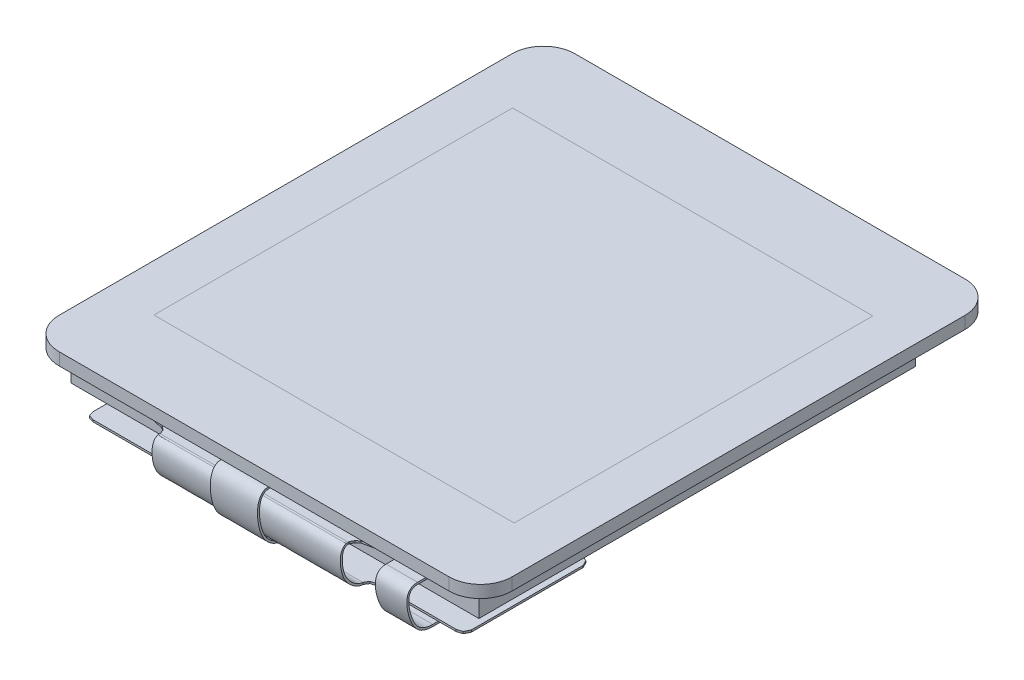
SolidWorks part; units mm, degrees
ref_plane "Ebene vorne" through (0, 0, 0) normal (0, 0, 1) x (1, 0, 0)
ref_plane "Ebene oben" through (0, 0, 0) normal (0, 1, 0) x (1, 0, 0)
ref_plane "Ebene rechts" through (0, 0, 0) normal (1, 0, 0) x (0, 0, -1)
sketch "Skizze1" plane through (0, 0, 0) normal (0, 1, 0) x (1, 0, 0)
  line L0 (-10.3006, -18.7379) -> (-10.4888, -18.361)
  line L1 (10.2585, -18.6958) -> (10.4, -18.361)
  line L4 (-14.0273, -22.8411) -> (-14.0273, -22.7993)
  line L5 (-14.0273, -22.7993) -> (-14.0691, -22.7993)
  line L6 (-14.0691, -22.7993) -> (-14.0691, -22.8411)
  line L7 (-14.0691, -22.8411) -> (-14.0273, -22.8411)
  line L8 (15.7018, -18.361) -> (15.7018, 15.346)
  line L9 (15.7018, 15.346) -> (-15.7858, 15.346)
  line L10 (-15.7858, 15.346) -> (-15.7858, -18.361)
  line L11 (-15.7858, -18.361) -> (15.7018, -18.361)
  line L12 (12.5614, -22.7993) -> (12.5614, -18.361)
  line L13 (10.1331, -22.7993) -> (10.1331, -18.361)
  line L14 (10.1331, -26.3167) -> (10.1331, -18.361)
  line L15 (12.5614, -26.3167) -> (12.5614, -18.361)
  line L16 (10.7611, -26.3167) -> (10.1331, -26.3167)
  line L17 (11.724, -26.3167) -> (10.9705, -26.3167)
  line L18 (11.5986, -26.0233) -> (11.5146, -26.3167)
  line L19 (11.1799, -26.3167) -> (11.0959, -26.0234)
  line L20 (10.9705, -26.3167) -> (10.9705, -26.2327)
  line L21 (10.9705, -26.2327) -> (10.8448, -26.1909)
  line L22 (10.8448, -26.1909) -> (10.7612, -26.2327)
  line L23 (10.7612, -26.2327) -> (10.7612, -26.3167)
  line L24 (10.6354, -26.0233) -> (10.4678, -26.3167)
  line L25 (12.2267, -26.3167) -> (12.1009, -26.0234)
  line L26 (12.0173, -26.3167) -> (11.9334, -26.2327)
  line L27 (11.9334, -26.2327) -> (11.8916, -26.1909)
  line L28 (11.8916, -26.1909) -> (11.724, -26.2327)
  line L29 (11.724, -26.2327) -> (11.724, -26.3167)
  line L30 (12.5614, -26.3167) -> (12.0173, -26.3167)
  line L31 (11.5986, -25.0187) -> (11.5986, -24.0137)
  line L32 (11.5986, -24.0137) -> (12.1009, -24.0137)
  line L33 (12.1009, -24.0137) -> (12.1009, -25.0187)
  line L34 (11.5986, -25.0187) -> (11.5146, -25.2699)
  line L35 (11.5146, -25.2699) -> (11.5986, -25.4792)
  line L36 (11.8915, -25.1441) -> (11.724, -25.1859)
  line L37 (11.724, -25.1859) -> (11.724, -25.3535)
  line L38 (11.724, -25.3535) -> (11.8915, -25.3953)
  line L39 (11.8915, -25.3953) -> (11.9334, -25.3535)
  line L40 (11.9334, -25.3535) -> (12.0173, -25.2699)
  line L41 (12.0173, -25.2699) -> (11.9334, -25.1859)
  line L42 (11.9334, -25.1859) -> (11.8915, -25.1441)
  line L43 (12.1009, -25.4792) -> (12.2267, -25.2699)
  line L44 (12.2267, -25.2699) -> (12.1009, -25.0187)
  line L45 (10.6354, -25.3535) -> (10.6354, -24.0137)
  line L46 (11.0959, -24.0137) -> (11.0959, -25.3535)
  line L47 (11.0959, -25.814) -> (11.0959, -26.0234)
  line L48 (10.6354, -25.814) -> (10.6354, -26.0234)
  line L49 (10.6354, -25.3535) -> (10.4678, -25.5628)
  line L50 (10.4678, -25.5628) -> (10.6354, -25.814)
  line L51 (10.8447, -25.3953) -> (10.7612, -25.4792)
  line L52 (10.7612, -25.4792) -> (10.7612, -25.6046)
  line L53 (10.7612, -25.6046) -> (10.8447, -25.6886)
  line L54 (10.8447, -25.6886) -> (10.9705, -25.6046)
  line L55 (10.9705, -25.6046) -> (10.9705, -25.4792)
  line L56 (10.9705, -25.4792) -> (10.8447, -25.3953)
  line L57 (11.0959, -25.814) -> (11.1799, -25.5628)
  line L58 (11.1799, -25.5628) -> (11.0959, -25.3535)
  line L59 (12.1009, -26.0233) -> (12.1009, -25.4792)
  line L60 (11.5986, -25.4792) -> (11.5986, -26.0233)
  line L61 (10.6354, -24.0137) -> (11.0959, -24.0137)
  line L62 (-13.9015, -13.8387) -> (-13.9015, 13.8387)
  line L63 (-13.9015, 13.8387) -> (13.9015, 13.8387)
  line L64 (13.9015, 13.8387) -> (13.9015, -13.8387)
  line L65 (13.9015, -13.8387) -> (-13.9015, -13.8387)
  line L77 (-7.3278, -19.8683) -> (-7.3278, -22.3806)
  line L78 (-10.1749, -18.8215) -> (-7.7465, -19.366)
  line L80 (-10.3006, -18.7379) -> (-10.1749, -18.8215)
  line L81 (-7.3278, -19.8683) -> (-7.4532, -19.5754)
  line L82 (-7.4532, -19.5754) -> (-7.7465, -19.366)
  line L83 (-7.3278, -19.8683) -> (-7.3278, -22.3806)
  line L84 (-7.7883, -22.8411) -> (-7.4532, -22.7158)
  line L85 (-7.4532, -22.7158) -> (-7.3278, -22.3806)
  line L86 (10.0491, -18.8215) -> (7.6207, -19.366)
  line L87 (10.0491, -18.8215) -> (10.2167, -18.7379)
  line L88 (10.2167, -18.7379) -> (10.2585, -18.6958)
  line L89 (7.6207, -19.366) -> (7.3696, -19.5754)
  line L90 (7.3696, -19.5754) -> (7.202, -19.8683)
  line L91 (7.202, -19.8683) -> (7.202, -22.3806)
  line L92 (3.5171, -58.2648) -> (-3.5593, -58.2648)
  line L93 (3.7265, -52.8214) -> (-3.7686, -52.8214)
  line L94 (3.5171, -58.2648) -> (3.6847, -58.223)
  line L95 (3.6847, -58.223) -> (3.7265, -58.0554)
  line L96 (3.7265, -53.2823) -> (3.7265, -33.8118)
  line L97 (-3.7687, -58.0554) -> (-3.6994, -58.223)
  line L98 (-3.6994, -58.223) -> (-3.5593, -58.2648)
  line L99 (-3.7687, -52.8214) -> (3.7265, -52.8214)
  line L100 (3.7265, -53.2823) -> (3.7265, -58.0554)
  line L101 (3.5171, -58.2648) -> (3.6847, -58.223)
  line L102 (3.6847, -58.223) -> (3.7265, -58.0554)
  line L103 (3.5171, -58.2648) -> (-3.5593, -58.2648)
  line L104 (-3.7687, -58.0554) -> (-3.6994, -58.223)
  line L105 (-3.6994, -58.223) -> (-3.5593, -58.2648)
  line L107 (-3.7687, -58.0554) -> (-3.7687, -33.8118)
  line L108 (-3.7687, -33.8118) -> (-4.1034, -32.9744)
  line L109 (-4.1034, -32.9744) -> (-5.0248, -32.6393)
  line L114 (13.9433, -22.8411) -> (7.7883, -22.8411)
  line L115 (-7.7883, -22.8411) -> (-14.0691, -22.8411)
  line L116 (-14.0691, -22.8411) -> (-14.4878, -22.9669)
  line L117 (-14.4878, -22.9669) -> (-14.6132, -23.3856)
  line L118 (7.202, -22.3806) -> (7.4114, -22.7158)
  line L119 (7.4114, -22.7158) -> (7.7883, -22.8412)
  line L120 (14.5714, -23.3856) -> (14.5714, -32.0112)
  line L121 (14.5714, -23.3856) -> (14.3621, -22.9669)
  line L122 (14.3621, -22.9669) -> (13.9434, -22.8412)
  line L123 (13.9433, -32.6393) -> (4.9409, -32.6393)
  line L124 (4.9409, -32.6393) -> (4.1034, -32.9744)
  line L125 (4.1034, -32.9744) -> (3.7265, -33.8118)
  line L126 (13.9433, -32.6393) -> (14.3621, -32.4299)
  line L127 (14.3621, -32.4299) -> (14.5714, -32.0112)
  line L128 (-5.0248, -32.6393) -> (-14.0691, -32.6393)
  line L129 (-14.6132, -23.3856) -> (-14.6132, -32.0112)
  line L130 (-14.6132, -32.0112) -> (-14.4878, -32.4299)
  line L131 (-14.4878, -32.4299) -> (-14.0691, -32.6393)
  line L132 (-3.0566, -25.3535) -> (-2.7219, -25.1859)
  line L133 (-2.7219, -25.1859) -> (-2.5961, -24.8512)
  line L134 (-2.5961, -24.8511) -> (-2.5961, -19.9519)
  line L135 (1.0466, -24.8511) -> (1.256, -25.1859)
  line L136 (1.256, -25.1859) -> (1.5911, -25.3535)
  line L137 (1.0466, -24.8511) -> (1.0466, -19.9519)
  line L138 (-8.5, -31.2995) -> (-11.3474, -31.2995)
  line L139 (-11.4728, -31.0901) -> (-11.4728, -31.2574)
  line L140 (-11.4728, -31.2574) -> (-11.3474, -31.2995)
  line L141 (-11.4728, -31.0901) -> (-11.4728, -27.9916)
  line L142 (-11.3474, -27.7822) -> (-11.4728, -27.824)
  line L143 (-11.4728, -27.824) -> (-11.4728, -27.9916)
  line L144 (-11.3474, -27.7822) -> (-8.5, -27.7822)
  line L145 (-8.5, -27.7822) -> (-8.5, -31.2995)
  line L146 (-11.4728, -31.0901) -> (-11.4728, -31.2574)
  line L147 (-11.4728, -31.2574) -> (-11.3474, -31.2995)
  line L148 (-11.4728, -31.0901) -> (-11.4728, -27.9916)
  line L149 (-11.3474, -27.7822) -> (-11.4728, -27.824)
  line L150 (-11.4728, -27.824) -> (-11.4728, -27.9916)
  line L151 (-11.3474, -27.7822) -> (-5.0248, -27.7822)
  line L152 (-5.0248, -27.7822) -> (-4.6897, -27.6146)
  line L153 (-4.6897, -27.6146) -> (-4.5221, -27.2795)
  line L154 (-14.0273, -22.8411) -> (-14.0273, -22.7993)
  line L155 (-14.0273, -22.7993) -> (-14.0691, -22.7993)
  line L156 (-14.0691, -22.7993) -> (-14.0691, -22.8411)
  line L157 (-14.0691, -22.8411) -> (-14.0273, -22.8411)
  line L158 (10.6354, -27.3635) -> (10.6354, -23.8044)
  line L159 (10.6354, -23.8044) -> (11.0959, -23.8044)
  line L160 (11.0959, -23.8044) -> (11.0959, -27.3635)
  line L161 (11.0959, -27.3635) -> (10.6354, -27.3635)
  line L162 (11.5986, -27.3635) -> (11.5986, -23.8044)
  line L163 (11.5986, -23.8044) -> (12.1009, -23.8044)
  line L164 (12.1009, -23.8044) -> (12.1009, -27.3635)
  line L165 (12.1009, -27.3635) -> (11.5986, -27.3635)
  line L166 (10.7611, -28.8708) -> (10.7611, -28.0334)
  line L167 (11.1799, -28.4521) -> (10.3424, -28.4521)
  line L168 (11.6822, -28.4521) -> (12.4778, -28.4521)
  line L169 (-7.7883, -24.1813) -> (-7.7883, -23.8044)
  line L170 (-7.7883, -23.8044) -> (-5.9877, -23.8044)
  line L171 (-5.9877, -23.8044) -> (-5.9877, -24.1813)
  line L172 (-5.9877, -24.1813) -> (-7.7883, -24.1813)
  line L173 (-7.7883, -24.8511) -> (-7.7883, -24.516)
  line L174 (-7.7883, -24.516) -> (-5.9877, -24.516)
  line L175 (-5.9877, -24.516) -> (-5.9877, -24.8511)
  line L176 (-5.9877, -24.8511) -> (-7.7883, -24.8511)
  line L177 (-7.7883, -25.4792) -> (-7.7883, -25.1441)
  line L178 (-7.7883, -25.1441) -> (-5.9877, -25.1441)
  line L179 (-5.9877, -25.1441) -> (-5.9877, -25.4792)
  line L180 (-5.9877, -25.4792) -> (-7.7883, -25.4792)
  line L181 (-7.7883, -26.1073) -> (-7.7883, -25.7722)
  line L182 (-7.7883, -25.7722) -> (-5.9877, -25.7722)
  line L183 (-5.9877, -25.7722) -> (-5.9877, -26.1073)
  line L184 (-5.9877, -26.1073) -> (-7.7883, -26.1073)
  line L185 (-11.8079, -24.1813) -> (-11.8079, -23.8044)
  line L186 (-11.8079, -23.8044) -> (-13.6504, -23.8044)
  line L187 (-13.6504, -23.8044) -> (-13.6504, -24.1813)
  line L188 (-13.6504, -24.1813) -> (-11.8079, -24.1813)
  line L189 (-11.8079, -24.8511) -> (-11.8079, -24.516)
  line L190 (-11.8079, -24.516) -> (-13.6504, -24.516)
  line L191 (-13.6504, -24.516) -> (-13.6504, -24.8511)
  line L192 (-13.6504, -24.8511) -> (-11.8079, -24.8511)
  line L193 (-11.8079, -25.4792) -> (-11.8079, -25.1441)
  line L194 (-11.8079, -25.1441) -> (-13.6504, -25.1441)
  line L195 (-13.6504, -25.1441) -> (-13.6504, -25.4792)
  line L196 (-13.6504, -25.4792) -> (-11.8079, -25.4792)
  line L197 (-11.8079, -26.1073) -> (-11.8079, -25.7722)
  line L198 (-11.8079, -25.7722) -> (-13.6504, -25.7722)
  line L199 (-13.6504, -25.7722) -> (-13.6504, -26.1073)
  line L200 (-13.6504, -26.1073) -> (-11.8079, -26.1073)
  line L201 (-11.3474, -31.2995) -> (-5.0248, -31.2995)
  line L202 (-4.5221, -31.8018) -> (-4.6897, -31.4667)
  line L203 (-4.6897, -31.4667) -> (-5.0248, -31.2995)
  line L204 (1.8005, -31.8018) -> (1.9262, -31.8018)
  line L205 (1.9262, -31.8018) -> (2.0098, -31.6343)
  line L206 (2.0098, -31.6343) -> (2.0098, -25.5628)
  line L207 (2.0098, -25.5628) -> (1.9262, -25.3953)
  line L208 (1.9262, -25.3953) -> (1.8005, -25.3535)
  line L209 (1.8005, -25.3535) -> (-4.3128, -25.3535)
  line L210 (-4.3128, -25.3535) -> (-4.4803, -25.3953)
  line L211 (-4.4803, -25.3953) -> (-4.5221, -25.5628)
  line L212 (-4.5221, -25.5628) -> (-4.5221, -31.6343)
  line L213 (-4.5221, -31.6343) -> (-4.4803, -31.8018)
  line L214 (-4.4803, -31.8018) -> (-4.3128, -31.8018)
  line L215 (-4.3128, -31.8018) -> (1.8005, -31.8018)
  line L216 (14.9901, -19.9519) -> (16.2463, -19.6589)
  line L217 (16.2463, -19.6589) -> (17.1674, -18.7379)
  line L218 (17.1674, -18.7379) -> (17.4189, -17.5235)
  line L219 (17.4189, -17.5235) -> (17.4189, 17.4396)
  line L220 (17.4189, 17.4396) -> (17.1674, 18.6957)
  line L221 (17.1674, 18.6957) -> (16.2463, 19.575)
  line L222 (16.2463, 19.575) -> (14.9902, 19.8683)
  line L223 (14.9901, 19.8683) -> (-15.0741, 19.8683)
  line L224 (-15.0741, 19.8683) -> (-16.2881, 19.575)
  line L225 (-16.2881, 19.575) -> (-17.1677, 18.6957)
  line L226 (-17.1677, 18.6957) -> (-17.5442, 17.4396)
  line L227 (-17.5443, 17.4396) -> (-17.5443, -17.5236)
  line L228 (-17.5443, -17.5235) -> (-17.1677, -18.7379)
  line L229 (-17.1677, -18.7379) -> (-16.2881, -19.6589)
  line L230 (-16.2881, -19.6589) -> (-15.0741, -19.9519)
  line L231 (-15.0741, -19.9519) -> (14.9902, -19.9519)
  line L232 (-13.9015, 13.8387) -> (-13.9015, -13.8387)
  line L233 (-13.9015, -13.8387) -> (13.9015, -13.8387)
  line L234 (13.9015, -13.8387) -> (13.9015, 13.8387)
  line L235 (13.9015, 13.8387) -> (-13.9015, 13.8387)
  line L236 (-12.5659, -28.1971) -> (-12.5659, -28.5322)
  line L237 (-12.5659, -28.5322) -> (-13.3197, -28.5322)
  line L238 (-13.3197, -28.5322) -> (-13.3197, -28.1971)
  line L239 (-13.3197, -28.1971) -> (-12.5659, -28.1971)
  line L240 (-12.5659, -28.6998) -> (-12.5659, -29.0349)
  line L241 (-12.5659, -29.0349) -> (-13.3197, -29.0349)
  line L242 (-13.3197, -29.0349) -> (-13.3197, -28.6998)
  line L243 (-13.3197, -28.6998) -> (-12.5659, -28.6998)
  line L244 (-12.5659, -29.2439) -> (-12.5659, -29.4951)
  line L245 (-12.5659, -29.4951) -> (-13.3197, -29.4951)
  line L246 (-13.3197, -29.4951) -> (-13.3197, -29.2439)
  line L247 (-13.3197, -29.2439) -> (-12.5659, -29.2439)
  line L248 (-12.5659, -29.7048) -> (-12.5659, -29.9977)
  line L249 (-12.5659, -29.9977) -> (-13.3197, -29.9977)
  line L250 (-13.3197, -29.9977) -> (-13.3197, -29.7048)
  line L251 (-13.3197, -29.7048) -> (-12.5659, -29.7048)
  line L252 (-12.5659, -30.2071) -> (-12.5659, -30.5001)
  line L253 (-12.5659, -30.5001) -> (-13.3197, -30.5001)
  line L254 (-13.3197, -30.5001) -> (-13.3197, -30.2071)
  line L255 (-13.3197, -30.2071) -> (-12.5659, -30.2071)
  line L256 (-12.5659, -30.7094) -> (-12.5659, -31.0446)
  line L257 (-12.5659, -31.0446) -> (-13.3197, -31.0446)
  line L258 (-13.3197, -31.0446) -> (-13.3197, -30.7094)
  line L259 (-13.3197, -30.7094) -> (-12.5659, -30.7094)
  point P1 (0, 0)
  point P2 (0, 0)
  point P82 (0, 0)
  point P84 (0, 0)
sketch "Skizze3" plane through (0, 0, 0) normal (0, 1, 0) x (1, 0, 0)
  line L0 (15.7018, -18.361) -> (15.7018, 15.346)
  line L1 (-15.7858, 15.346) -> (15.7018, 15.346)
  line L2 (-15.7858, 15.346) -> (-15.7858, -18.361)
  line L3 (-15.7858, -18.361) -> (15.7018, -18.361)
  point P0 (0, 0)
extrude "Aufsatz-Linear austragen1" add sketch "Skizze3" along normal blind 2.275
sketch "Skizze2" plane through (0, 0, 0) normal (0, 1, 0) x (1, 0, 0)
  line L3 (17.4189, -17.5232) -> (17.4189, 17.4396)
  line L7 (14.9901, 19.8683) -> (-15.0741, 19.8683)
  line L11 (-17.5443, 17.4396) -> (-17.5443, -17.5236)
  line L15 (-15.0741, -19.9519) -> (14.9902, -19.9519)
  arc A0 (-17.5443, 17.4396) -> (-15.0741, 19.8683) centre (-15.1152, 17.4396) cw
  arc A1 (14.9901, 19.8683) -> (17.4189, 17.4396) centre (14.9901, 17.4396) cw
  arc A2 (-17.5443, -17.5236) -> (-15.0741, -19.9519) centre (-15.1156, -17.5236) ccw
  arc A3 (14.9902, -19.9519) -> (17.4189, -17.5232) centre (14.9902, -17.5232) ccw
  point P0 (0, 0)
extrude "Aufsatz-Linear austragen2" add sketch "Skizze2" along normal offset from surface (0.95 mm away) 3.225 from surface separate body up to face at (-0.042, 0, 1.5075) starting at face at (-0.042, 2.275, 1.5075)
sketch "Skizze4" plane through (0, 3.225, 0) normal (0, 1, 0) x (1, 0, 0)
  line L0 (-13.9015, -13.8387) -> (-13.9015, 13.8387)
  line L1 (-13.9015, 13.8387) -> (13.9015, 13.8387)
  line L2 (13.9015, 13.8387) -> (13.9015, -13.8387)
  line L3 (13.9015, -13.8387) -> (-13.9015, -13.8387)
  point P0 (0, 0)
split line "Trennlinie1"
sketch "Skizze5" plane through (0, 0, 0) normal (0, 1, 0) x (1, 0, 0)
  line L0 (-10.3006, -18.7379) -> (-10.4888, -18.361)
  line L1 (-7.3278, -19.9519) -> (7.202, -19.9519)
  line L7 (-7.3278, -19.8683) -> (-7.4532, -19.5754)
  line L9 (10.0491, -18.8215) -> (7.6207, -19.366)
  line L10 (7.202, -19.9519) -> (7.202, -19.8683)
  line L11 (-15.0741, -19.9519) -> (14.9902, -19.9519) construction
  line L12 (7.3696, -19.5754) -> (7.6207, -19.366)
  line L13 (7.3696, -19.5754) -> (7.202, -19.8683)
  line L14 (10.0491, -18.8215) -> (10.1331, -18.7796)
  line L15 (-10.3006, -18.7379) -> (-10.1749, -18.8215)
  line L16 (-7.7465, -19.366) -> (-7.4532, -19.5754)
  line L17 (-10.4888, -18.361) -> (12.5614, -18.361)
  line L18 (10.1331, -19.9519) -> (12.5614, -19.9519)
  line L19 (-7.3278, -19.8683) -> (-7.3278, -19.9519)
  line L20 (10.1331, -18.7796) -> (10.1331, -19.9519)
  line L21 (12.5614, -18.361) -> (12.5614, -19.9519)
  line L22 (-10.1749, -18.8215) -> (-7.7465, -19.366)
  point P1 (0, 0)
extrude "Aufsatz-Linear austragen3" add sketch "Skizze5" along normal blind 0.15 from offset 1.5 separate body contours L15 L22 L16 L7 L19 L1 L10 L13 L12 L9 L14 L20 L18 L21 L17 L0 region at (1.315, 0, 19.1017)
sketch "Skizze6" plane through (0, 0, 0) normal (0, 1, 0) x (1, 0, 0)
  line L2 (-2.5961, -19.9519) -> (-2.5961, -18.361)
  line L3 (-15.7858, -18.361) -> (15.7018, -18.361) construction
  line L4 (-2.5961, -19.9519) -> (1.0466, -19.9519)
  line L5 (-2.5961, -18.361) -> (1.0466, -18.361)
  line L6 (-10.4888, -18.361) -> (12.5614, -18.361) construction
  line L7 (1.0466, -18.361) -> (1.0466, -19.9519)
  point P0 (0, 0)
extrude "Aufsatz-Linear austragen4" add sketch "Skizze6" against normal blind 0.15 from surface separate body starting at face at (-0.042, 2.275, 1.5075)
sketch "Skizze7" plane through (0, 0, 0) normal (0, 1, 0) x (1, 0, 0)
  line L194 (-13.3197, -10.4927) -> (-12.5659, -10.4927)
  line L195 (-13.3197, -10.1576) -> (-13.3197, -10.4927)
  line L196 (-12.5659, -10.1576) -> (-13.3197, -10.1576)
  line L197 (-12.5659, -10.4927) -> (-12.5659, -10.1576)
  line L198 (-13.3197, -10.995) -> (-12.5659, -10.995)
  line L199 (-13.3197, -10.7021) -> (-13.3197, -10.995)
  line L200 (-12.5659, -10.7021) -> (-13.3197, -10.7021)
  line L201 (-12.5659, -10.995) -> (-12.5659, -10.7021)
  line L202 (-13.3197, -11.4974) -> (-12.5659, -11.4974)
  line L203 (-13.3197, -11.2044) -> (-13.3197, -11.4974)
  line L204 (-12.5659, -11.2044) -> (-13.3197, -11.2044)
  line L205 (-12.5659, -11.4974) -> (-12.5659, -11.2044)
  line L206 (-13.3197, -11.9582) -> (-12.5659, -11.9582)
  line L207 (-13.3197, -11.7071) -> (-13.3197, -11.9582)
  line L208 (-12.5659, -11.7071) -> (-13.3197, -11.7071)
  line L209 (-12.5659, -11.9582) -> (-12.5659, -11.7071)
  line L210 (-13.3197, -12.5023) -> (-12.5659, -12.5023)
  line L211 (-13.3197, -12.1672) -> (-13.3197, -12.5023)
  line L212 (-12.5659, -12.1672) -> (-13.3197, -12.1672)
  line L213 (-12.5659, -12.5023) -> (-12.5659, -12.1672)
  line L214 (-13.3197, -13.005) -> (-12.5659, -13.005)
  line L215 (-13.3197, -12.6699) -> (-13.3197, -13.005)
  line L216 (-12.5659, -12.6699) -> (-13.3197, -12.6699)
  line L217 (-12.5659, -13.005) -> (-12.5659, -12.6699)
  line L218 (-9.5538, -5.8259) -> (-3.4405, -5.8259)
  line L219 (-9.7213, -5.8259) -> (-9.5537, -5.8259)
  line L220 (-9.7631, -5.9934) -> (-9.7213, -5.8259)
  line L221 (-9.7631, -12.0649) -> (-9.7631, -5.9934)
  line L222 (-9.7213, -12.2324) -> (-9.7631, -12.0649)
  line L223 (-9.5538, -12.2742) -> (-9.7213, -12.2324)
  line L224 (-3.4405, -12.2742) -> (-9.5537, -12.2742)
  line L225 (-3.3147, -12.2324) -> (-3.4405, -12.2742)
  line L226 (-3.2311, -12.0649) -> (-3.3147, -12.2324)
  line L227 (-3.2311, -5.9934) -> (-3.2311, -12.0649)
  line L228 (-3.3147, -5.8259) -> (-3.2311, -5.9934)
  line L229 (-3.4405, -5.8259) -> (-3.3147, -5.8259)
  line L230 (-9.9307, -6.161) -> (-10.2658, -6.3282)
  line L231 (-9.7631, -5.8259) -> (-9.9307, -6.161)
  line L232 (-11.3474, -9.9026) -> (-5.0248, -9.9026)
  line L233 (-13.6504, -15.0948) -> (-11.8079, -15.0948)
  line L234 (-13.6504, -15.43) -> (-13.6504, -15.0948)
  line L235 (-11.8079, -15.43) -> (-13.6504, -15.43)
  line L236 (-11.8079, -15.0948) -> (-11.8079, -15.43)
  line L237 (-13.6504, -15.7229) -> (-11.8079, -15.7229)
  line L238 (-13.6504, -16.058) -> (-13.6504, -15.7229)
  line L239 (-11.8079, -16.058) -> (-13.6504, -16.058)
  line L240 (-11.8079, -15.7229) -> (-11.8079, -16.058)
  line L241 (-13.6504, -16.351) -> (-11.8079, -16.351)
  line L242 (-13.6504, -16.6861) -> (-13.6504, -16.351)
  line L243 (-11.8079, -16.6861) -> (-13.6504, -16.6861)
  line L244 (-11.8079, -16.351) -> (-11.8079, -16.6861)
  line L245 (-13.6504, -17.0209) -> (-11.8079, -17.0209)
  line L246 (-13.6504, -17.3978) -> (-13.6504, -17.0209)
  line L247 (-11.8079, -17.3978) -> (-13.6504, -17.3978)
  line L248 (-11.8079, -17.0209) -> (-11.8079, -17.3978)
  line L249 (-5.9877, -15.0948) -> (-7.7883, -15.0948)
  line L250 (-5.9877, -15.43) -> (-5.9877, -15.0948)
  line L251 (-7.7883, -15.43) -> (-5.9877, -15.43)
  line L252 (-7.7883, -15.0948) -> (-7.7883, -15.43)
  line L253 (-5.9877, -15.7229) -> (-7.7883, -15.7229)
  line L254 (-5.9877, -16.058) -> (-5.9877, -15.7229)
  line L255 (-7.7883, -16.058) -> (-5.9877, -16.058)
  line L256 (-7.7883, -15.7229) -> (-7.7883, -16.058)
  line L257 (-5.9877, -16.351) -> (-7.7883, -16.351)
  line L258 (-5.9877, -16.6861) -> (-5.9877, -16.351)
  line L259 (-7.7883, -16.6861) -> (-5.9877, -16.6861)
  line L260 (-7.7883, -16.351) -> (-7.7883, -16.6861)
  line L261 (-5.9877, -17.0209) -> (-7.7883, -17.0209)
  line L262 (-5.9877, -17.3978) -> (-5.9877, -17.0209)
  line L263 (-7.7883, -17.3978) -> (-5.9877, -17.3978)
  line L264 (-7.7883, -17.0209) -> (-7.7883, -17.3978)
  line L265 (11.6822, -12.7501) -> (12.4778, -12.7501)
  line L266 (11.1799, -12.7501) -> (10.3424, -12.7501)
  line L267 (10.7611, -12.3313) -> (10.7611, -13.1688)
  line L268 (12.1009, -13.8387) -> (11.5986, -13.8387)
  line L269 (12.1009, -17.3978) -> (12.1009, -13.8387)
  line L270 (11.5986, -17.3978) -> (12.1009, -17.3978)
  line L271 (11.5986, -13.8387) -> (11.5986, -17.3978)
  line L272 (11.0959, -13.8387) -> (10.6354, -13.8387)
  line L273 (11.0959, -17.3978) -> (11.0959, -13.8387)
  line L274 (10.6354, -17.3978) -> (11.0959, -17.3978)
  line L275 (10.6354, -13.8387) -> (10.6354, -17.3978)
  line L280 (-9.9306, -10.0131) -> (-9.7631, -10.3482)
  line L281 (-10.2658, -9.8455) -> (-9.9306, -10.0131)
  line L282 (-22.0679, -9.8455) -> (-10.2658, -9.8455)
  line L283 (-11.4728, -13.3782) -> (-11.4728, -13.2106)
  line L284 (-22.0679, -9.8455) -> (-11.4728, -13.3782)
  line L285 (-11.4728, -10.112) -> (-11.4728, -13.2106)
  line L286 (-11.4728, -9.9448) -> (-11.3474, -9.9026)
  line L287 (-11.4728, -10.112) -> (-11.4728, -9.9448)
  line L288 (-8.5, -13.42) -> (-8.5, -9.9026)
  line L289 (-22.0679, -9.8455) -> (-8.5, -13.42)
  line L290 (-11.4728, -13.3782) -> (-11.4728, -13.2106)
  line L291 (-22.0679, -9.8455) -> (-11.4728, -13.3782)
  line L292 (-11.4728, -10.112) -> (-11.4728, -13.2106)
  line L293 (-11.4728, -9.9448) -> (-11.3474, -9.9026)
  line L294 (-11.4728, -10.112) -> (-11.4728, -9.9448)
  line L295 (-8.5, -9.9026) -> (-11.3474, -9.9026)
  line L296 (-3.985, -12.4418) -> (-3.6499, -12.2742)
  line L297 (-4.1944, -12.7766) -> (-3.985, -12.4418)
  line L298 (-7.9628, -12.4418) -> (-7.8371, -12.7766)
  line L299 (-8.2976, -12.2742) -> (-7.9628, -12.4418)
  line L300 (-14.4878, -8.7722) -> (-14.0691, -8.5629)
  line L301 (-14.6132, -9.191) -> (-14.4878, -8.7722)
  line L302 (-14.6132, -17.8165) -> (-14.6132, -9.1909)
  line L303 (-5.0248, -8.5629) -> (-14.0691, -8.5629)
  line L304 (14.3621, -8.7722) -> (14.5714, -9.191)
  line L305 (13.9433, -8.5629) -> (14.3621, -8.7722)
  line L306 (4.1034, -8.2277) -> (3.7265, -7.3903)
  line L307 (4.9409, -8.5629) -> (4.1034, -8.2277)
  line L308 (13.9433, -8.5629) -> (4.9409, -8.5629)
  line L309 (14.3621, -18.2352) -> (13.9434, -18.361)
  line L310 (14.5714, -17.8165) -> (14.3621, -18.2352)
  line L311 (14.5714, -17.8165) -> (14.5714, -9.1909)
  line L312 (7.4114, -18.4864) -> (7.7883, -18.361)
  line L313 (7.202, -18.8215) -> (7.4114, -18.4864)
  line L314 (-14.4878, -18.2352) -> (-14.6132, -17.8165)
  line L315 (-14.0691, -18.361) -> (-14.4878, -18.2352)
  line L316 (-7.7883, -18.361) -> (-14.0691, -18.361)
  line L317 (13.9433, -18.361) -> (7.7883, -18.361)
  line L318 (-4.1034, -8.2277) -> (-5.0248, -8.5629)
  line L319 (-3.7687, -7.3903) -> (-4.1034, -8.2277)
  line L320 (-3.7687, 16.8533) -> (-3.7687, -7.3903)
  line L321 (-3.6994, 17.0208) -> (-3.5593, 17.0627)
  line L322 (-3.7687, 16.8533) -> (-3.6994, 17.0208)
  line L323 (3.5171, 17.0626) -> (-3.5593, 17.0626)
  line L324 (3.6847, 17.0208) -> (3.7265, 16.8533)
  line L325 (3.5171, 17.0626) -> (3.6847, 17.0208)
  line L326 (3.7265, 12.0802) -> (3.7265, 16.8533)
  line L327 (-3.7687, 11.6193) -> (3.7265, 11.6193)
  line L328 (-3.6994, 17.0208) -> (-3.5593, 17.0627)
  line L329 (-3.7687, 16.8533) -> (-3.6994, 17.0208)
  line L330 (3.7265, 12.0802) -> (3.7265, -7.3903)
  line L331 (3.6847, 17.0208) -> (3.7265, 16.8533)
  line L332 (3.5171, 17.0626) -> (3.6847, 17.0208)
  line L333 (3.7265, 11.6193) -> (-3.7686, 11.6193)
  line L334 (3.5171, 17.0626) -> (-3.5593, 17.0626)
  line L335 (-7.4532, -18.4864) -> (-7.3278, -18.8215)
  line L336 (-7.7883, -18.361) -> (-7.4532, -18.4864)
  line L337 (10.6354, -17.1884) -> (11.0959, -17.1884)
  line L338 (11.5986, -15.7229) -> (11.5986, -15.1788)
  line L339 (12.1009, -15.1788) -> (12.1009, -15.7229)
  line L340 (11.1799, -15.6393) -> (11.0959, -15.8487)
  line L341 (11.0959, -15.3882) -> (11.1799, -15.6393)
  line L342 (10.9705, -15.7229) -> (10.8447, -15.8069)
  line L343 (10.9705, -15.5975) -> (10.9705, -15.7229)
  line L344 (10.8447, -15.5136) -> (10.9705, -15.5975)
  line L345 (10.7612, -15.5975) -> (10.8447, -15.5136)
  line L346 (10.7612, -15.7229) -> (10.7612, -15.5975)
  line L347 (10.8447, -15.8069) -> (10.7612, -15.7229)
  line L348 (10.4678, -15.6393) -> (10.6354, -15.3881)
  line L349 (10.6354, -15.8487) -> (10.4678, -15.6393)
  line L350 (10.6354, -15.3882) -> (10.6354, -15.1788)
  line L351 (11.0959, -15.3882) -> (11.0959, -15.1788)
  line L352 (11.0959, -17.1884) -> (11.0959, -15.8487)
  line L353 (10.6354, -15.8487) -> (10.6354, -17.1884)
  line L354 (12.2267, -15.9323) -> (12.1009, -16.1834)
  line L355 (12.1009, -15.7229) -> (12.2267, -15.9323)
  line L356 (11.9334, -16.0162) -> (11.8915, -16.058)
  line L357 (12.0173, -15.9323) -> (11.9334, -16.0162)
  line L358 (11.9334, -15.8487) -> (12.0173, -15.9323)
  line L359 (11.8915, -15.8069) -> (11.9334, -15.8487)
  line L360 (11.724, -15.8487) -> (11.8915, -15.8069)
  line L361 (11.724, -16.0162) -> (11.724, -15.8487)
  line L362 (11.8915, -16.058) -> (11.724, -16.0162)
  line L363 (11.5146, -15.9323) -> (11.5986, -15.7229)
  line L364 (11.5986, -16.1834) -> (11.5146, -15.9323)
  line L365 (12.1009, -17.1884) -> (12.1009, -16.1834)
  line L366 (11.5986, -17.1884) -> (12.1009, -17.1884)
  line L367 (11.5986, -16.1834) -> (11.5986, -17.1884)
  line L368 (12.5614, -14.8855) -> (12.0173, -14.8855)
  line L369 (11.724, -14.9694) -> (11.724, -14.8855)
  line L370 (11.8916, -15.0112) -> (11.724, -14.9694)
  line L371 (11.9334, -14.9694) -> (11.8916, -15.0112)
  line L372 (12.0173, -14.8855) -> (11.9334, -14.9694)
  line L373 (12.2267, -14.8855) -> (12.1009, -15.1788)
  line L374 (10.6354, -15.1788) -> (10.4678, -14.8855)
  line L375 (10.7612, -14.9694) -> (10.7612, -14.8855)
  line L376 (10.8448, -15.0112) -> (10.7612, -14.9694)
  line L377 (10.9705, -14.9694) -> (10.8448, -15.0112)
  line L378 (10.9705, -14.8855) -> (10.9705, -14.9694)
  line L379 (11.1799, -14.8855) -> (11.0959, -15.1788)
  line L380 (11.5986, -15.1788) -> (11.5146, -14.8855)
  line L381 (11.724, -14.8855) -> (10.9705, -14.8855)
  line L382 (10.7611, -14.8855) -> (10.1331, -14.8855)
  point P0 (-5.241, -9.9504)
  point P1 (0, 0)
  point P2 (0, 0)
sketch "Skizze8" plane through (0, 0, 0) normal (0, 1, 0) x (1, 0, 0)
  line L24 (-7.3278, -18.8215) -> (7.202, -18.8215)
  line L25 (7.7883, -18.361) -> (13.9433, -18.361)
  line L26 (-3.7687, -7.3903) -> (-4.1034, -8.2277)
  line L27 (3.7265, -7.3903) -> (4.1034, -8.2277)
  line L28 (4.9409, -8.5629) -> (13.9433, -8.5629)
  line L29 (14.3621, -8.7722) -> (14.5714, -9.1909)
  line L30 (14.5714, -17.8165) -> (14.3621, -18.2352)
  line L31 (7.7883, -18.361) -> (7.4114, -18.4864)
  line L32 (-5.0248, -8.5629) -> (-14.0691, -8.5629)
  line L33 (-14.4878, -8.7722) -> (-14.6132, -9.1909)
  line L34 (-14.6132, -17.8165) -> (-14.4878, -18.2352)
  line L35 (-14.0691, -18.361) -> (-7.7883, -18.361)
  line L36 (-7.4532, -18.4864) -> (-7.3278, -18.8215)
  line L37 (4.1034, -8.2277) -> (4.9409, -8.5629)
  line L38 (13.9433, -8.5629) -> (14.3621, -8.7722)
  line L71 (14.5714, -9.1909) -> (14.5714, -17.8165)
  line L72 (14.3621, -18.2352) -> (13.9433, -18.361)
  line L73 (7.4114, -18.4864) -> (7.202, -18.8215)
  line L82 (-7.4532, -18.4864) -> (-7.7883, -18.361)
  line L83 (-14.0691, -18.361) -> (-14.4878, -18.2352)
  line L84 (-14.6132, -17.8165) -> (-14.6132, -9.1909)
  line L85 (-5.0248, -8.5629) -> (-4.1034, -8.2277)
  line L86 (-14.4878, -8.7722) -> (-14.0691, -8.5629)
  line L87 (-3.7687, -7.3903) -> (-3.7687, 16.8533)
  line L89 (3.7265, -7.3903) -> (3.7265, 16.8533)
  line L90 (-3.5593, 17.0627) -> (3.5171, 17.0627)
  line L91 (-3.7687, 16.8533) -> (-3.6994, 17.0208)
  line L92 (3.7265, 16.8533) -> (3.6847, 17.0209)
  line L93 (-3.6994, 17.0208) -> (-3.5593, 17.0627)
  line L94 (3.5171, 17.0627) -> (3.6847, 17.0209)
  line L119 (13.9433, -18.361) -> (7.7883, -18.361)
  point P1 (0, 0)
extrude "Aufsatz-Linear austragen5" add sketch "Skizze8" against normal blind 0.15 from offset 1.6 separate body contours L94 L90 L93 L91 L87 L26 L85 L32 L86 L33 L84 L34 L83 L35 L82 L36 L24 L73 L31 L25 L72 L30 L71 L29 L38 L28 L37 L27 L89 L92 region at (-0.0228, 0, 6.5169) offset against normal yes
sketch "Skizze9" plane through (0, 0, 0) normal (0, 1, 0) x (1, 0, 0)
  line L0 (-2.5961, -18.7299) -> (1.0466, -18.7299)
  line L1 (-3.0566, -15.8487) -> (-4.3128, -15.8487)
  line L2 (-5.0248, -13.42) -> (-4.6897, -13.5875)
  line L3 (-4.5221, -13.9226) -> (-4.5221, -15.6393)
  line L4 (-4.4803, -15.8069) -> (-4.3128, -15.8487)
  line L5 (-3.0566, -15.8487) -> (-2.7219, -16.0162)
  line L6 (1.0466, -16.351) -> (1.256, -16.0162)
  line L7 (1.5911, -15.8487) -> (1.8005, -15.8487)
  line L9 (1.9262, -15.8069) -> (2.0098, -15.6393)
  line L10 (-11.3474, -9.9026) -> (-11.4728, -9.9448)
  line L11 (-11.3474, -13.42) -> (-11.4728, -13.3782)
  line L12 (-4.6897, -13.5875) -> (-4.5221, -13.9226)
  line L13 (-4.5221, -15.6393) -> (-4.4803, -15.8069)
  line L14 (-2.7219, -16.0162) -> (-2.5961, -16.351)
  line L16 (-5.0248, -9.9026) -> (-4.6897, -9.7354)
  line L17 (1.256, -16.0162) -> (1.5911, -15.8487)
  line L18 (2.0098, -15.6393) -> (2.0098, -9.5679)
  line L19 (-4.6897, -9.7354) -> (-4.5221, -9.4003)
  line L20 (-5.0248, -9.9026) -> (-11.3474, -9.9026)
  line L38 (-4.5221, -9.4003) -> (1.9262, -9.4003)
  line L45 (1.9262, -15.8069) -> (1.8005, -15.8487)
  line L48 (1.9262, -9.4003) -> (2.0098, -9.5679)
  line L58 (-11.4728, -9.9448) -> (-11.4728, -13.3782)
  line L62 (-11.3474, -13.42) -> (-5.0248, -13.42)
  line L65 (-11.4728, -9.9448) -> (-11.4728, -13.3782)
  line L69 (1.0466, -16.351) -> (1.0466, -18.7299)
  line L72 (-2.5961, -16.351) -> (-2.5961, -18.7299)
  point P0 (0, 0)
extrude "Aufsatz-Linear austragen6" add sketch "Skizze9" against normal blind 0.15 from surface separate body contours L14 L72 L0 L69 L6 L17 L7 L45 L9 L18 L48 L38 L19 L16 L20 L10 L58 L11 L62 L2 L12 L3 L13 L4 L1 L5 region at (-3.3265, 0, 12.9576) starting at face at (-0.0326, -1.75, 7.3235)
sketch "Skizze10" plane through (0, 0, 0) normal (1, 0, 0) x (0, 0, -1)
  line L0 (-19.9519, 1.5) -> (-19.9519, 1.65)
  line L1 (-18.8215, -1.6) -> (-18.8215, -1.75)
  line L4 (-20.1019, 1.6299) -> (-20.1019, 1.65) construction
  line L5 (-18.9715, -1.7346) -> (-18.9715, -1.75) construction
  arc A0 (-20.1019, 1.6299) -> (-19.9519, 1.65) centre (-19.9567, 1.1166) cw
  arc A1 (-18.8215, -1.75) -> (-18.9715, -1.7346) centre (-18.8215, -1.0126) cw
  spline S0 degree 3 poles (-19.9519, 1.5) (-20.5381, 1.5) (-20.4456, 0.116) (-19.8473, -1.1972) (-19.1556, -1.6) (-18.8215, -1.6) knots 0 0 0 0 0.401622 0.501622 1 1 1 1
  spline S1 degree 1 poles (-20.1019, 1.6299) (-18.9715, -1.7346) knots 0 0 1 1 construction
  spline S2 degree 3 poles (-20.1019, 1.6299) (-20.1984, 1.6026) (-20.3769, 1.4788) (-20.5455, 1.1191) (-20.5815, 0.5548) (-20.4618, -0.1651) (-20.2543, -0.6952) (-19.971, -1.0991) (-19.6408, -1.4173) (-19.2913, -1.6365) (-19.0848, -1.7125) (-18.9715, -1.7346) knots 0.026925 0.026925 0.026925 0.026925 0.084237 0.14155 0.256175 0.3708 0.485424 0.600049 0.714674 0.829299 0.943924 0.943924 0.943924 0.943924
  dimension "D1" = 0.15
extrude "Aufsatz-Linear austragen7" add sketch "Skizze10" along normal up to vertex (7.202 mm away) and the other way up to vertex (7.3278 mm away) up to point (7.202, 1.5, 19.9519) other way up to point (-7.3278, -1.75, 18.8215)
sketch "Skizze11" plane through (0, 0, 0) normal (1, 0, 0) x (0, 0, -1)
  line L0 (-18.7299, -1.9) -> (-18.7299, -1.75)
  line L1 (-19.9519, 2.275) -> (-19.9519, 2.125)
  spline S0 degree 3 poles (-19.9519, 2.275) (-20.7319, 2.275) (-20.9442, 0.9749) (-20.3068, -1.5688) (-19.3098, -1.9) (-18.7299, -1.9) knots 0 0 0 0 0.380799 0.480799 1 1 1 1
  spline S1 degree 1 poles (-19.9519, 2.125) (-18.7299, -1.75) knots 0 0 1 1 construction
  spline S2 degree 3 poles (-19.9519, 2.125) (-20.0429, 2.125) (-20.2356, 2.0811) (-20.4795, 1.8553) (-20.7534, 1.041) (-20.4523, -0.7497) (-19.7491, -1.4807) (-19.1373, -1.7206) (-18.87, -1.75) (-18.7299, -1.75) knots 0 0 0 0 0.0625 0.125 0.25 0.5 0.75 0.875 1 1 1 1
  point P5 (-20.9467, -0.2254)
  point P8 (-20.6788, -0.0591)
  dimension "D1" = 0.15
extrude "Aufsatz-Linear austragen8" add sketch "Skizze11" against normal up to vertex (2.5961 mm away) and the other way up to vertex (1.0466 mm away) up to point (-2.5961, 2.275, 19.9519) other way up to point (1.0466, 2.275, 19.9519)
sketch "Skizze12" plane through (0, 0, 0) normal (0, 1, 0) x (1, 0, 0)
  line L0 (10.6354, -14.8855) -> (10.6354, -15.4029)
  line L1 (10.6354, -17.1884) -> (11.0959, -17.1884)
  line L2 (11.0959, -17.1884) -> (11.0959, -15.8757)
  line L3 (11.5986, -14.8855) -> (11.5986, -15.7247)
  line L10 (11.5986, -17.1884) -> (12.1009, -17.1884)
  line L11 (12.1009, -17.1884) -> (12.1009, -16.1527)
  line L12 (10.1331, -14.8855) -> (10.7557, -14.8855)
  line L13 (10.9757, -14.8855) -> (11.7397, -14.8855)
  line L14 (11.9597, -14.8855) -> (12.5614, -14.8855)
  line L15 (11.5986, -16.1527) -> (11.5986, -17.1884)
  line L24 (12.1009, -15.7247) -> (12.1009, -14.8855)
  line L25 (10.6354, -15.8757) -> (10.6354, -17.1884)
  line L26 (11.0959, -15.4029) -> (11.0959, -14.8855)
  line L40 (10.1331, -18.7796) -> (10.1331, -14.8855)
  line L41 (12.5614, -14.8855) -> (12.5614, -18.7796)
  line L42 (12.5614, -18.361) -> (12.5614, -19.9519) construction
  line L43 (12.5614, -18.7796) -> (10.1331, -18.7796)
  circle A0 centre (10.8657, -15.6393) radius 0.15
  circle A1 centre (11.8497, -15.9387) radius 0.15
  arc A2 (11.0959, -15.8757) -> (11.0959, -15.4029) centre (10.8657, -15.6393) ccw
  arc A3 (11.5986, -15.7247) -> (11.5986, -16.1527) centre (11.8497, -15.9387) ccw
  arc A4 (10.7557, -14.8855) -> (10.9757, -14.8855) centre (10.8657, -14.8855) ccw
  arc A5 (11.7397, -14.8855) -> (11.9597, -14.8855) centre (11.8497, -14.8855) ccw
  arc A6 (10.6354, -15.4029) -> (10.6354, -15.8757) centre (10.8657, -15.6393) ccw
  arc A7 (12.1009, -16.1527) -> (12.1009, -15.7247) centre (11.8497, -15.9387) ccw
  point P0 (0, 0)
extrude "Aufsatz-Linear austragen9" add sketch "Skizze12" against normal blind 0.15 from surface separate body contours A7 L11 L10 L15 A3 L3 L13 L26 A2 L2 L1 L25 A6 L0 L12 L40 L43 L41 L14 L24 | L11 A7 L24 L14 A5 L13 L3 A3 L15 L10 A1 | L0 A6 L25 L1 L2 A2 L26 L13 A4 L12 A0 region at (10.8657, 0, 16.0594) region at (11.3385, 0, 17.0967) region at (11.6692, 0, 14.9094) starting at face at (-0.1199, -1.75, 8.6708)
sketch "Skizze13" plane through (0, 0, 0) normal (1, 0, 0) x (0, 0, -1)
  line L0 (-19.9519, 1.65) -> (-19.9519, 1.5)
  line L2 (-18.7796, -1.9) -> (-18.7796, -1.75)
  spline S0 degree 3 poles (-19.9519, 1.65) (-21.0132, 1.65) (-20.7532, -0.6413) (-19.8315, -1.9) (-18.7796, -1.9) knots 0 0 0 0 0.524833 1 1 1 1
  spline S1 degree 3 poles (-19.9519, 2.275) (-20.7319, 2.275) (-20.9442, 0.9749) (-20.3068, -1.5688) (-19.3098, -1.9) (-18.7299, -1.9) knots 0 0 0 0 0.380799 0.480799 1 1 1 1 construction
  spline S2 degree 1 poles (-19.9519, 1.5) (-18.7796, -1.75) knots 0 0 1 1 construction
  spline S3 degree 3 poles (-19.9519, 1.5) (-20.0469, 1.5) (-20.2589, 1.4692) (-20.4279, 1.3625) (-20.5514, 1.2012) (-20.6483, 0.8978) (-20.6413, 0.3828) (-20.4703, -0.3059) (-20.2312, -0.9183) (-19.9137, -1.3771) (-19.5419, -1.6228) (-19.1541, -1.7304) (-18.8998, -1.75) (-18.7796, -1.75) knots 0 0 0 0 0.0625 0.125 0.1875 0.25 0.375 0.5 0.625 0.75 0.875 0.9375 1 1 1 1
  dimension "D1" = 0.15
extrude "Aufsatz-Linear austragen11" add sketch "Skizze13" along normal up to vertex (12.5614 mm away) from vertex up to point (12.5614, 1.65, 19.9519) starting at point (10.1331, 1.65, 19.9519)
sketch "Skizze14" plane through (0, -1.75, 0) normal (0, 1, 0) x (1, 0, 0)
  line L0 (-13.3197, -10.4927) -> (-12.5659, -10.4927)
  line L1 (-13.3197, -10.1576) -> (-13.3197, -10.4927)
  line L2 (-12.5659, -10.1576) -> (-13.3197, -10.1576)
  line L3 (-12.5659, -10.4927) -> (-12.5659, -10.1576)
  line L4 (-13.3197, -10.995) -> (-12.5659, -10.995)
  line L5 (-13.3197, -10.7021) -> (-13.3197, -10.995)
  line L6 (-12.5659, -10.7021) -> (-13.3197, -10.7021)
  line L7 (-12.5659, -10.995) -> (-12.5659, -10.7021)
  line L8 (-13.3197, -11.4974) -> (-12.5659, -11.4974)
  line L9 (-13.3197, -11.2044) -> (-13.3197, -11.4974)
  line L10 (-12.5659, -11.2044) -> (-13.3197, -11.2044)
  line L11 (-12.5659, -11.4974) -> (-12.5659, -11.2044)
  line L12 (-13.3197, -11.9582) -> (-12.5659, -11.9582)
  line L13 (-13.3197, -11.7071) -> (-13.3197, -11.9582)
  line L14 (-12.5659, -11.7071) -> (-13.3197, -11.7071)
  line L15 (-12.5659, -11.9582) -> (-12.5659, -11.7071)
  line L16 (-13.3197, -12.5023) -> (-12.5659, -12.5023)
  line L17 (-13.3197, -12.1672) -> (-13.3197, -12.5023)
  line L18 (-12.5659, -12.1672) -> (-13.3197, -12.1672)
  line L19 (-12.5659, -12.5023) -> (-12.5659, -12.1672)
  line L20 (-13.3197, -13.005) -> (-12.5659, -13.005)
  line L21 (-13.3197, -12.6699) -> (-13.3197, -13.005)
  line L22 (-12.5659, -12.6699) -> (-13.3197, -12.6699)
  line L23 (-12.5659, -13.005) -> (-12.5659, -12.6699)
  line L24 (-13.6504, -15.0948) -> (-11.8079, -15.0948)
  line L25 (-13.6504, -15.43) -> (-13.6504, -15.0948)
  line L26 (-11.8079, -15.43) -> (-13.6504, -15.43)
  line L27 (-11.8079, -15.0948) -> (-11.8079, -15.43)
  line L28 (-13.6504, -15.7229) -> (-11.8079, -15.7229)
  line L29 (-13.6504, -16.058) -> (-13.6504, -15.7229)
  line L30 (-11.8079, -16.058) -> (-13.6504, -16.058)
  line L31 (-11.8079, -15.7229) -> (-11.8079, -16.058)
  line L32 (-13.6504, -16.351) -> (-11.8079, -16.351)
  line L33 (-13.6504, -16.6861) -> (-13.6504, -16.351)
  line L34 (-11.8079, -16.6861) -> (-13.6504, -16.6861)
  line L35 (-11.8079, -16.351) -> (-11.8079, -16.6861)
  line L36 (-13.6504, -17.0209) -> (-11.8079, -17.0209)
  line L37 (-13.6504, -17.3978) -> (-13.6504, -17.0209)
  line L38 (-11.8079, -17.3978) -> (-13.6504, -17.3978)
  line L39 (-11.8079, -17.0209) -> (-11.8079, -17.3978)
  line L40 (-5.9877, -15.0948) -> (-7.7883, -15.0948)
  line L41 (-5.9877, -15.43) -> (-5.9877, -15.0948)
  line L42 (-7.7883, -15.43) -> (-5.9877, -15.43)
  line L43 (-7.7883, -15.0948) -> (-7.7883, -15.43)
  line L44 (-5.9877, -15.7229) -> (-7.7883, -15.7229)
  line L45 (-5.9877, -16.058) -> (-5.9877, -15.7229)
  line L46 (-7.7883, -16.058) -> (-5.9877, -16.058)
  line L47 (-7.7883, -15.7229) -> (-7.7883, -16.058)
  line L48 (-5.9877, -16.351) -> (-7.7883, -16.351)
  line L49 (-5.9877, -16.6861) -> (-5.9877, -16.351)
  line L50 (-7.7883, -16.6861) -> (-5.9877, -16.6861)
  line L51 (-7.7883, -16.351) -> (-7.7883, -16.6861)
  line L52 (-5.9877, -17.0209) -> (-7.7883, -17.0209)
  line L53 (-5.9877, -17.3978) -> (-5.9877, -17.0209)
  line L54 (-7.7883, -17.3978) -> (-5.9877, -17.3978)
  line L55 (-7.7883, -17.0209) -> (-7.7883, -17.3978)
  line L56 (12.1009, -13.8387) -> (11.5986, -13.8387)
  line L57 (12.1009, -17.3978) -> (12.1009, -13.8387)
  line L58 (11.5986, -17.3978) -> (12.1009, -17.3978)
  line L59 (11.5986, -13.8387) -> (11.5986, -17.3978)
  line L60 (11.0959, -13.8387) -> (10.6354, -13.8387)
  line L61 (11.0959, -17.3978) -> (11.0959, -13.8387)
  line L62 (10.6354, -17.3978) -> (11.0959, -17.3978)
  line L63 (10.6354, -13.8387) -> (10.6354, -17.3978)
  line L64 (11.0959, -17.1884) -> (11.0959, -15.8487)
  line L65 (10.6354, -15.8487) -> (10.6354, -17.1884)
  line L66 (12.1009, -17.1884) -> (12.1009, -16.1834)
  line L67 (11.5986, -16.1834) -> (11.5986, -17.1884)
  point P0 (0, 0)
split line "Trennlinie2"
sketch "Skizze16" plane through (0, -1.9, 0) normal (0, -1, 0) x (1, 0, 0)
  line L0 (10.7557, 14.8855) -> (10.6354, 14.8855)
  line L1 (11.9597, 14.8855) -> (12.1009, 14.8855)
  line L2 (11.5986, 14.8855) -> (11.7397, 14.8855)
  line L12 (11.0959, 15.4029) -> (11.0959, 14.8855)
  line L13 (10.6354, 15.8757) -> (10.6354, 17.1884)
  line L14 (12.1009, 15.7247) -> (12.1009, 14.8855)
  line L15 (11.5986, 16.1527) -> (11.5986, 17.1884)
  line L16 (10.9757, 14.8855) -> (11.0959, 14.8855)
  line L17 (12.1009, 17.1884) -> (12.1009, 16.1527)
  line L18 (11.5986, 17.1884) -> (12.1009, 17.1884)
  line L19 (11.5986, 14.8855) -> (11.5986, 15.7247)
  line L20 (11.0959, 17.1884) -> (11.0959, 15.8757)
  line L21 (10.6354, 17.1884) -> (11.0959, 17.1884)
  line L22 (10.6354, 14.8855) -> (10.6354, 15.4029)
  arc A8 (12.1009, 16.1527) -> (12.1009, 15.7247) centre (11.8497, 15.9387) cw
  arc A9 (10.6354, 15.4029) -> (10.6354, 15.8757) centre (10.8657, 15.6393) cw
  arc A10 (11.7397, 14.8855) -> (11.9597, 14.8855) centre (11.8497, 14.8855) cw
  arc A11 (10.7557, 14.8855) -> (10.9757, 14.8855) centre (10.8657, 14.8855) cw
  arc A12 (11.5986, 15.7247) -> (11.5986, 16.1527) centre (11.8497, 15.9387) cw
  arc A13 (11.0959, 15.8757) -> (11.0959, 15.4029) centre (10.8657, 15.6393) cw
  circle A14 centre (11.8497, 15.9387) radius 0.15
  circle A15 centre (10.8657, 15.6393) radius 0.15
  point P73 (0, 0)
split line "Trennlinie3"
sketch "Skizze17" plane through (0, 0, 14.8855) normal (0, 0, -1) x (-1, 0, 0)
  line L0 (-10.6354, -1.9) -> (-10.6354, -1.75)
  line L1 (-10.6354, -1.75) -> (-11.0959, -1.75)
  line L2 (-11.0959, -1.75) -> (-11.0959, -1.9)
  line L3 (-11.0959, -1.9) -> (-10.6354, -1.9)
  line L4 (-11.5986, -1.9) -> (-11.5986, -1.75)
  line L5 (-11.5986, -1.75) -> (-12.1009, -1.75)
  line L6 (-12.1009, -1.75) -> (-12.1009, -1.9)
  line L7 (-12.1009, -1.9) -> (-11.5986, -1.9)
split line "Trennlinie4"
